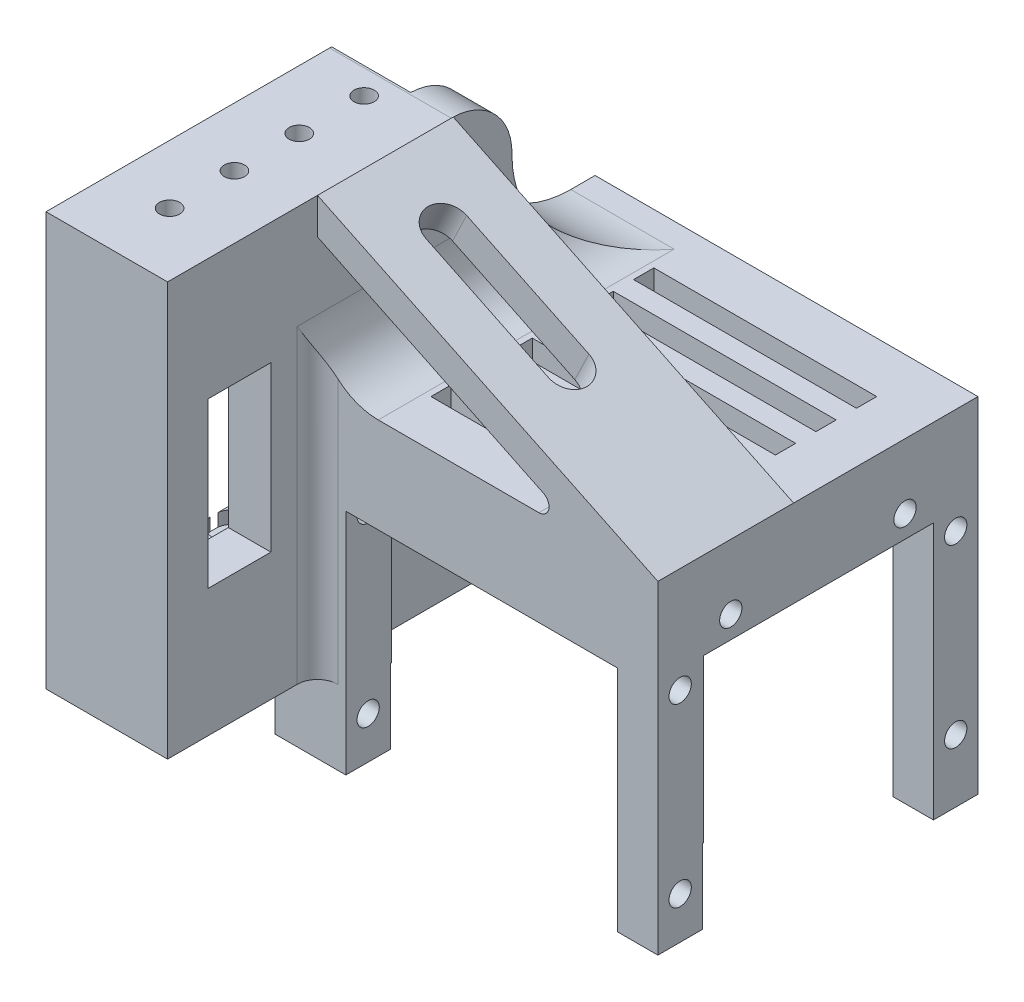
SolidWorks part; units mm, degrees
ref_plane "Front Plane" through (0, 0, 0) normal (0, 0, 1) x (1, 0, 0)
ref_plane "Top Plane" through (0, 0, 0) normal (0, 1, 0) x (1, 0, 0)
ref_plane "Right Plane" through (0, 0, 0) normal (1, 0, 0) x (0, 0, -1)
sketch "Sketch1" plane through (0, 0, 0) normal (0, 0, 1) x (1, 0, 0)
  line L1 (0, 0) -> (57.912, 0)
  line L2 (0, 0) -> (0, 63.754)
  line L3 (0, 63.754) -> (57.912, 63.754)
  line L4 (57.912, 0) -> (57.912, 63.754)
  dimension "D1" = 57.912
  dimension "D2" = 63.754
extrude "Boss-Extrude1" add sketch "Sketch1" against normal blind 58.928
sketch "Sketch3" plane through (0, 0, 0) normal (0, 0, 1) x (1, 0, 0)
  line L0 (42.672, 63.754) -> (0, 43.18)
  line L1 (42.672, 59.2423) -> (14.3644, 45.594)
  line L2 (14.9159, 43.18) -> (42.672, 43.18)
  line L3 (44.437, 60.0933) -> (1.765, 39.5193) construction
  line L4 (0, 63.754) -> (0, 0)
  line L5 (0, 0) -> (57.912, 0)
  line L6 (57.912, 0) -> (57.912, 63.754)
  line L7 (57.912, 63.754) -> (0, 63.754)
  line L8 (0, 63.754) -> (0, 43.18)
  line L9 (5.08, 0) -> (5.08, 31.242)
  line L10 (0, 0) -> (57.912, 0) construction
  line L11 (42.672, 63.754) -> (0, 63.754)
  line L12 (42.672, 59.2423) -> (42.672, 43.18)
  line L13 (5.08, 31.242) -> (39.116, 31.242)
  line L14 (39.116, 31.242) -> (39.116, 0)
  line L15 (5.08, 0) -> (39.116, 0)
  line L16 (48.006, 0) -> (48.006, 11.938)
  line L17 (48.006, 11.938) -> (57.912, 11.938)
  line L18 (57.912, 0) -> (57.912, 63.754) construction
  line L19 (57.912, 11.938) -> (57.912, 0)
  line L20 (48.006, 0) -> (57.912, 0)
  arc A0 (14.3644, 45.594) -> (14.9159, 43.18) centre (14.9159, 44.45) ccw
  dimension "D5" = 1.27
  dimension "D2" = 15.24
  dimension "D3" = 20.574
  dimension "D7" = 5.08
  dimension "D8" = 31.242
  dimension "D9" = 34.036
  dimension "D10" = 9.906
  dimension "D11" = 11.938
  dimension "D1" = 0
  dimension "D4" = 4.064
extrude "Cut-Extrude1" cut sketch "Sketch3" against normal through all
sketch "Sketch4" plane through (0, 63.754, 0) normal (0, 1, 0) x (1, 0, 0)
  line L0 (0, 0) -> (0, 18.796)
  line L1 (0, 58.928) -> (0, 0) construction
  line L2 (0, 18.796) -> (42.672, 18.796)
  line L3 (42.672, 58.928) -> (42.672, 0) construction
  line L4 (42.672, 18.796) -> (42.672, 0)
  line L5 (42.672, 0) -> (0, 0)
  line L6 (57.912, 35.814) -> (48.006, 35.814)
  line L7 (57.912, 58.928) -> (57.912, 0) construction
  line L8 (48.006, 35.814) -> (48.006, 58.928)
  line L9 (48.006, 58.928) -> (57.912, 58.928)
  line L10 (57.912, 58.928) -> (57.912, 35.814)
  line L11 (50.546, 35.814) -> (50.546, 32.512) construction
  circle A0 centre (50.546, 32.512) radius 1.27
  circle A1 centre (50.546, 24.384) radius 1.27
  circle A2 centre (50.546, 16.256) radius 1.27
  circle A3 centre (50.546, 8.128) radius 1.27
  dimension "D5" = 2.54
  dimension "D1" = 18.796
  dimension "D2" = 9.906
  dimension "D3" = 7.366
  dimension "D4" = 3.302
  dimension "D8" = 35.814
  dimension "D6" = 4
extrude "Cut-Extrude2" cut sketch "Sketch4" against normal through all
fillet "Fillet1" radius 2.54 1 edges at (42.672, 21.59, -18.796)
sketch "Sketch6" plane through (0, 63.754, 0) normal (0, 1, 0) x (1, 0, 0)
  line L0 (42.672, 35.814) -> (0, 35.814)
  line L1 (0, 58.928) -> (0, 18.796) construction
  line L2 (0, 35.814) -> (0, 58.928)
  line L3 (0, 58.928) -> (48.006, 58.928)
  line L4 (48.006, 58.928) -> (48.006, 43.18)
  line L5 (48.006, 58.928) -> (48.006, 35.814) construction
  line L6 (48.006, 43.18) -> (42.672, 43.18)
  line L7 (42.672, 58.928) -> (42.672, 18.796) construction
  line L8 (42.672, 43.18) -> (42.672, 35.814)
  line L9 (48.006, 35.814) -> (57.912, 35.814) construction
  dimension "D1" = 15.748
extrude "Cut-Extrude3" cut sketch "Sketch6" against normal blind 20.574
fillet "Fillet2" radius 12.7 1 edges at (45.339, 43.18, -43.18)
fillet "Fillet3" radius 7.62 1 edges at (42.672, 43.18, -36.068)
fillet "Fillet4" radius 7.62 1 edges at (45.339, 63.754, -43.18)
sketch "Sketch7" plane through (-16.8922, 35.0356, 0) normal (-0.4343, 0.9008, 0) x (0.9008, 0.4343, 0)
  line L0 (57.4899, 18.796) -> (57.4899, 24.638) construction
  line L1 (18.753, 18.796) -> (66.1259, 18.796) construction
  line L2 (57.4899, 24.638) -> (66.1259, 24.638) construction
  line L4 (57.4899, 24.638) -> (40.4719, 24.638)
  line L5 (57.4899, 29.718) -> (40.4719, 29.718)
  line L6 (66.1259, 35.56) -> (66.1259, 18.796) construction
  arc A0 (40.4719, 29.718) -> (40.4719, 24.638) centre (40.4719, 27.178) ccw
  arc A1 (57.4899, 29.718) -> (57.4899, 24.638) centre (57.4899, 27.178) cw
  dimension "D1" = 8.636
  dimension "D2" = 5.842
  dimension "D4" = 17.018
  dimension "D3" = 5.08
extrude "Cut-Extrude4" cut sketch "Sketch7" along direction (-0.4343, 0.9008, 0) on the side against the normal up to next (4.064 mm away)
sketch "Sketch8" plane through (0, 43.18, 0) normal (0, 1, 0) x (1, 0, 0)
  line L0 (6.35, 52.578) -> (34.29, 52.578)
  line L1 (34.29, 52.578) -> (34.29, 50.038)
  line L2 (34.29, 50.038) -> (6.35, 50.038)
  line L3 (6.35, 50.038) -> (6.35, 52.578)
  line L4 (0, 58.928) -> (0, 35.814) construction
  line L5 (0, 58.928) -> (48.006, 58.928) construction
  line L6 (34.29, 44.958) -> (6.35, 44.958)
  line L7 (34.29, 47.498) -> (34.29, 44.958)
  line L8 (6.35, 47.498) -> (34.29, 47.498)
  line L9 (6.35, 44.958) -> (6.35, 47.498)
  line L10 (34.29, 39.878) -> (6.35, 39.878)
  line L11 (34.29, 42.418) -> (34.29, 39.878)
  line L12 (6.35, 42.418) -> (34.29, 42.418)
  line L13 (6.35, 39.878) -> (6.35, 42.418)
  line L14 (34.29, 37.338) -> (20.574, 37.338)
  line L15 (34.29, 37.338) -> (34.29, 34.798)
  line L16 (34.29, 34.798) -> (20.574, 34.798)
  line L17 (20.574, 34.798) -> (20.574, 37.338)
  line L18 (34.29, 37.338) -> (6.35, 37.338) construction
  line L19 (34.29, 29.718) -> (20.574, 29.718)
  line L20 (34.29, 32.258) -> (34.29, 29.718)
  line L21 (34.29, 32.258) -> (20.574, 32.258)
  line L22 (20.574, 29.718) -> (20.574, 32.258)
  line L23 (34.29, 24.638) -> (20.574, 24.638)
  line L24 (34.29, 27.178) -> (34.29, 24.638)
  line L25 (34.29, 27.178) -> (20.574, 27.178)
  line L26 (20.574, 24.638) -> (20.574, 27.178)
  dimension "D1" = 6.35
  dimension "D2" = 6.35
  dimension "D3" = 2.54
  dimension "D4" = 27.94
  dimension "D7" = 2.54
  dimension "D8" = 13.716
  dimension "D6" = 2.54
  dimension "D5" = 3
  dimension "D9" = 3
extrude "Cut-Extrude5" cut sketch "Sketch8" against normal through all
sketch "Sketch9" plane through (0, 31.242, 0) normal (0, -1, 0) x (1, 0, 0)
  line L4 (39.116, -19.304) -> (5.08, -19.304)
  line L5 (5.08, -58.42) -> (39.116, -58.42)
  line L8 (39.116, -58.928) -> (39.116, -18.796)
  line L9 (39.116, -18.796) -> (5.08, -18.796)
  line L10 (5.08, -18.796) -> (5.08, -58.928)
  line L11 (5.08, -58.928) -> (39.116, -58.928)
  line L12 (39.116, -58.42) -> (39.116, -19.304)
  line L14 (5.08, -19.304) -> (5.08, -58.42)
  dimension "D1" = 0
extrude "Cut-Extrude6" cut sketch "Sketch9" against normal blind 5.588
sketch "Sketch10" plane through (5.08, 0, 0) normal (1, 0, 0) x (0, 0, -1)
  line L0 (58.42, 31.242) -> (54.6195, 36.83)
  line L1 (58.42, 36.83) -> (19.304, 36.83) construction
  line L2 (58.928, 31.242) -> (58.42, 31.242) construction
  line L3 (54.6195, 36.83) -> (58.42, 36.83)
  line L4 (58.42, 36.83) -> (58.42, 31.242)
  dimension "D1" = 124.22
extrude "Boss-Extrude3" add sketch "Sketch10" along direction (1, 0, 0) on the side of the normal up to next (34.036 mm away)
sketch "Sketch11" plane through (0, 31.242, 0) normal (0, -1, 0) x (1, 0, 0)
  line L0 (22.098, -58.928) -> (22.098, -18.796) construction
  line L1 (39.116, -58.928) -> (5.08, -58.928) construction
  line L2 (39.116, -18.796) -> (5.08, -18.796) construction
  line L3 (22.098, -38.862) -> (6.9192, -38.862) construction
ref_plane "Plane1" through (0, 0, -38.862) normal (0, 0, 1) x (1, 0, 0)
mirror "Mirror1" about plane through (0, 0, -38.862) normal (0, 0, 1) of "Boss-Extrude3"
fillet "Fillet5" radius 3.048 2 edges at (22.098, 36.83, -54.6195) (22.098, 36.83, -23.1045)
sketch "Sketch12" plane through (42.672, 0, 0) normal (-1, 0, 0) x (0, 0, 1)
  line L0 (0, 0) -> (0, 63.754) construction
  line L1 (-5.08, 27.94) -> (-12.954, 27.94)
  line L2 (-5.08, 27.94) -> (-5.08, 48.514)
  line L3 (-5.08, 48.514) -> (-12.954, 48.514)
  line L4 (-12.954, 27.94) -> (-12.954, 48.514)
  line L5 (0, 63.754) -> (-18.796, 63.754) construction
  line L6 (-53.34, 0) -> (-53.34, 11.938)
  line L7 (-58.928, 0) -> (-18.796, 0) construction
  line L8 (-53.34, 11.938) -> (-24.384, 11.938)
  line L9 (-24.384, 11.938) -> (-24.384, 2.5976)
  line L10 (-24.384, 2.5976) -> (-18.796, 2.5976)
  line L11 (-18.796, 0) -> (-18.796, 43.18) construction
  line L12 (-18.796, 2.5976) -> (-18.796, 11.938)
  line L13 (-18.796, 11.938) -> (0, 11.938)
  line L14 (0, 11.938) -> (0, 0)
  line L15 (0, 0) -> (-53.34, 0)
  line L16 (-58.928, 43.18) -> (-58.928, 0) construction
  dimension "D1" = 5.08
  dimension "D2" = 7.874
  dimension "D3" = 20.574
  dimension "D4" = 15.24
  dimension "D5" = 5.588
  dimension "D6" = 5.588
  dimension "D7" = 11.938
extrude "Cut-Extrude7" cut sketch "Sketch12" against normal through all both and the other way through all
sketch "Sketch14" plane through (0, 0, 0) normal (-1, 0, 0) x (0, 0, 1)
  line L0 (-53.34, 11.938) -> (-53.34, 32.258)
  line L1 (-53.34, 11.938) -> (-24.5287, 11.938)
  line L2 (-24.384, 11.938) -> (-53.34, 11.938) construction
  line L3 (-24.5287, 11.938) -> (-24.5287, 32.258)
  line L4 (-24.5287, 32.258) -> (-53.34, 32.258)
  dimension "D1" = 20.32
extrude "Cut-Extrude8" cut sketch "Sketch14" against normal up to surface (42.672 mm away) up to face at (42.672, 38.227, -9.017)
sketch "Sketch17" plane through (0, 0, 0) normal (-1, 0, 0) x (0, 0, 1)
  line L0 (-58.928, 0) -> (-53.34, 0) construction
  line L1 (-56.134, 0) -> (-56.134, 7.874) construction
  line L2 (-21.59, 2.5976) -> (-21.59, 0) construction
  line L3 (-18.796, 2.5976) -> (-24.384, 2.5976) construction
  line L4 (-38.862, 0) -> (-38.862, 39.1109) construction
  line L5 (-56.134, 0) -> (-21.59, 0) construction
  line L6 (-49.784, 32.258) -> (-49.784, 35.052) construction
  line L7 (-24.5287, 32.258) -> (-53.34, 32.258) construction
  circle A0 centre (-56.134, 7.874) radius 1.397
  circle A1 centre (-56.134, 29.972) radius 1.397
  circle A2 centre (-49.784, 35.052) radius 1.397
  circle A3 centre (-21.59, 7.874) radius 1.397
  circle A4 centre (-21.59, 29.972) radius 1.397
  circle A5 centre (-27.94, 35.052) radius 1.397
  dimension "D2" = 2.794
  dimension "D6" = 2.794
  dimension "D1" = 7.874
  dimension "D3" = 2
  dimension "D4" = 2.794
  dimension "D5" = 3.556
extrude "Cut-Extrude9" cut sketch "Sketch17" against normal through all
sketch "Sketch18" plane through (0, 0, -35.814) normal (0, 0, -1) x (-1, 0, 0)
  line L0 (-57.912, 58.6698) -> (-48.006, 58.6698)
  line L1 (-57.912, 11.938) -> (-57.912, 63.7498) construction
  line L2 (-48.006, 58.6698) -> (-48.006, 53.8438)
  line L3 (-48.006, 53.8438) -> (-53.086, 53.8438)
  line L4 (-53.086, 53.8438) -> (-53.086, 50.5418)
  line L5 (-53.086, 50.5418) -> (-48.006, 50.5418)
  line L6 (-48.006, 50.5418) -> (-48.006, 25.146)
  line L7 (-48.006, 37.8439) -> (-57.912, 37.8439) construction
  line L8 (-57.912, 17.018) -> (-57.912, 58.6698)
  line L9 (-57.912, 63.7519) -> (-57.912, 11.938) construction
  line L10 (-57.912, 63.754) -> (-57.912, 63.7498) construction
  line L11 (-48.006, 63.7498) -> (-57.912, 63.7498) construction
  line L12 (-57.912, 11.9359) -> (-57.912, 63.7498) construction
  line L13 (-53.086, 25.146) -> (-48.006, 25.146)
  line L14 (-53.086, 21.844) -> (-53.086, 25.146)
  line L15 (-48.006, 21.844) -> (-53.086, 21.844)
  line L16 (-48.006, 17.018) -> (-48.006, 21.844)
  line L17 (-57.912, 17.018) -> (-48.006, 17.018)
  point P15 (-57.912, 37.8449)
  dimension "D1" = 5.08
  dimension "D2" = 9.906
  dimension "D3" = 4.826
  dimension "D4" = 5.08
  dimension "D5" = 3.302
extrude "Cut-Extrude10" cut sketch "Sketch18" against normal blind 30.734
sketch "Sketch19" plane through (0, 25.146, 0) normal (0, 1, 0) x (1, 0, 0)
  circle A0 centre (50.546, 8.128) radius 1.27 construction
  circle A1 centre (50.546, 16.256) radius 1.27 construction
  circle A2 centre (50.546, 24.384) radius 1.27 construction
  circle A3 centre (50.546, 32.512) radius 1.27 construction
  circle A4 centre (50.546, 8.128) radius 1.27 construction
  circle A5 centre (50.546, 16.256) radius 1.27 construction
  circle A6 centre (50.546, 24.384) radius 1.27 construction
  circle A7 centre (50.546, 32.512) radius 1.27 construction
  circle A8 centre (50.546, 32.512) radius 2.5908
  circle A9 centre (50.546, 24.384) radius 2.5908
  circle A10 centre (50.546, 16.256) radius 2.5908
  circle A11 centre (50.546, 8.128) radius 2.5908
  dimension "D1" = 1.3208
  dimension "D2" = 1.3208
  dimension "D3" = 1.3208
  dimension "D4" = 1.3208
extrude "Cut-Extrude13" cut sketch "Sketch19" against normal blind 1.5875
sketch "Sketch20" plane through (0, 50.5418, 0) normal (0, -1, 0) x (1, 0, 0)
  circle A0 centre (50.546, -8.128) radius 1.27 construction
  circle A1 centre (50.546, -16.256) radius 1.27 construction
  circle A2 centre (50.546, -24.384) radius 1.27 construction
  circle A3 centre (50.546, -32.512) radius 1.27 construction
  circle A4 centre (50.546, -8.128) radius 1.27 construction
  circle A5 centre (50.546, -16.256) radius 1.27 construction
  circle A6 centre (50.546, -24.384) radius 1.27 construction
  circle A7 centre (50.546, -32.512) radius 1.27 construction
  circle A8 centre (50.546, -8.128) radius 2.5908
  circle A9 centre (50.546, -16.256) radius 2.5908
  circle A10 centre (50.546, -24.384) radius 2.5908
  circle A11 centre (50.546, -32.512) radius 2.5908
  dimension "D1" = 1.3208
  dimension "D2" = 1.3208
  dimension "D3" = 1.3208
  dimension "D4" = 1.3208
extrude "Cut-Extrude14" cut sketch "Sketch20" against normal blind 1.5875
mirror "Mirror2" about plane through (0, 0, 0) normal (0, 0, 1) of bodies 116
sketch "Sketch21" plane through (0, 63.754, 0) normal (0, 1, 0) x (1, 0, 0)
  line L0 (83.5536, 0) -> (-36.9665, 0)
  line L2 (-36.9665, 0) -> (-36.9665, 73.6411)
  line L3 (-36.9665, 73.6411) -> (83.5536, 73.6411)
  line L4 (83.5536, 73.6411) -> (83.5536, 0)
extrude "Cut-Extrude15" cut sketch "Sketch21" against normal through all
mirror "Mirror3" about plane through (57.912, 0, -58.928) normal (1, 0, 0) of bodies 118
sketch "Sketch22" plane through (0, 63.754, 0) normal (0, 1, 0) x (1, 0, 0)
  line L0 (57.912, 23.0082) -> (57.912, -82.454)
  line L2 (57.912, -82.454) -> (-28.6858, -82.454)
  line L3 (-28.6858, -82.454) -> (-28.6858, 23.0082)
  line L4 (-28.6858, 23.0082) -> (57.912, 23.0082)
extrude "Cut-Extrude16" cut sketch "Sketch22" against normal through all
mirror "Mirror4" about plane through (83.5536, 0, 0) normal (0, 0, 1) of bodies 120
sketch "Sketch23" plane through (0, 63.754, 0) normal (0, 1, 0) x (1, 0, 0)
  line L0 (13.8158, 0) -> (175.9481, 0)
  line L2 (175.9481, 0) -> (175.9481, -110.0388)
  line L3 (175.9481, -110.0388) -> (13.8158, -110.0388)
  line L4 (13.8158, -110.0388) -> (13.8158, 0)
extrude "Cut-Extrude17" cut sketch "Sketch23" against normal through all
